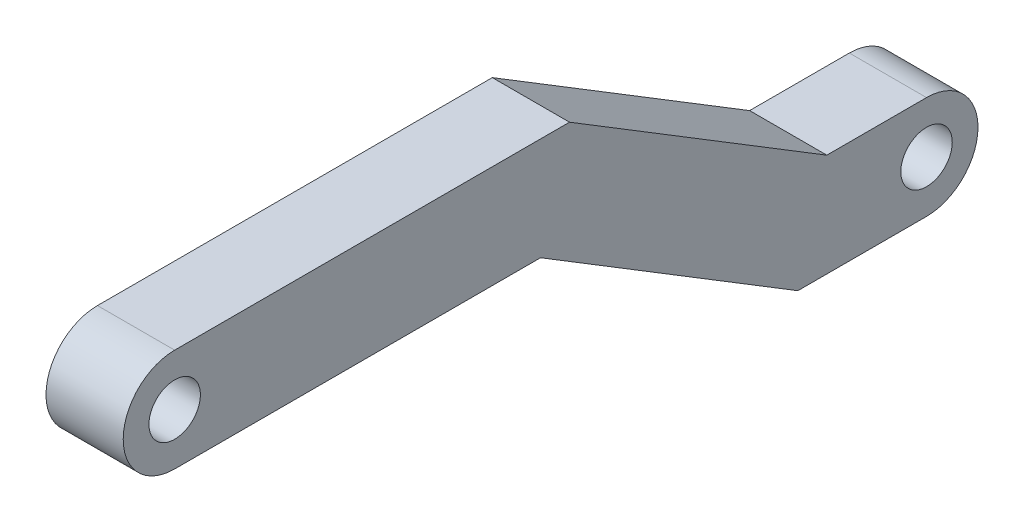
SolidWorks part; units mm, degrees
material "Plain Carbon Steel"
ref_plane "Front Plane" through (0, 0, 0) normal (0, 0, 1) x (1, 0, 0)
ref_plane "Top Plane" through (0, 0, 0) normal (0, 1, 0) x (1, 0, 0)
ref_plane "Right Plane" through (0, 0, 0) normal (1, 0, 0) x (0, 0, -1)
sketch "Sketch1" plane through (0, 0, 0) normal (1, 0, 0) x (0, 0, -1)
  line L4 (-16.09, -2) -> (16.09, -2)
  line L6 (-16.09, 2) -> (16.09, 2)
  line L8 (-16.09, -2) -> (16.09, 2) construction
  line L9 (-16.09, 2) -> (16.09, -2) construction
  arc A4 (16.09, 2) -> (16.09, -2) centre (16.09, 0) cw
  arc A5 (-16.09, 2) -> (-16.09, -2) centre (-16.09, 0) ccw
  circle A6 centre (-16.09, 0) radius 1
  circle A7 centre (16.09, 0) radius 1
  point P0 (0, 0)
  point P1 (0, 0)
  dimension "D2" = 4
  dimension "D3" = 2
  dimension "D1" = 32.18
sketch "Sketch2" plane through (0, 0, 0) normal (1, 0, 0) x (0, 0, -1)
  line L19 (-15.3433, -2) -> (13.8748, -8.1093) construction
  line L20 (10, -6.1093) -> (13.8748, -6.1093)
  line L21 (10, -6.1093) -> (0, 0)
  line L22 (0, 0) -> (-15.3433, 0)
  line L23 (8.8748, -10.1093) -> (13.8748, -10.1093)
  line L24 (8.8748, -10.1093) -> (-1.1252, -4)
  line L25 (-1.1252, -4) -> (-15.3433, -4)
  arc A6 (13.8748, -6.1093) -> (13.8748, -10.1093) centre (13.8748, -8.1093) cw
  arc A7 (-15.3433, 0) -> (-15.3433, -4) centre (-15.3433, -2) ccw
  circle A8 centre (-15.3433, -2) radius 1
  circle A9 centre (13.8748, -8.1093) radius 1
  dimension "D1" = 4
  dimension "D5" = 2
  dimension "D7" = 11.81
  dimension "D8" = 15
  dimension "D4" = 4
  dimension "D2" = 29.85
  dimension "D3" = 4
  dimension "D6" = 5
extrude "Boss-Extrude1" add sketch "Sketch2" along normal blind 3
